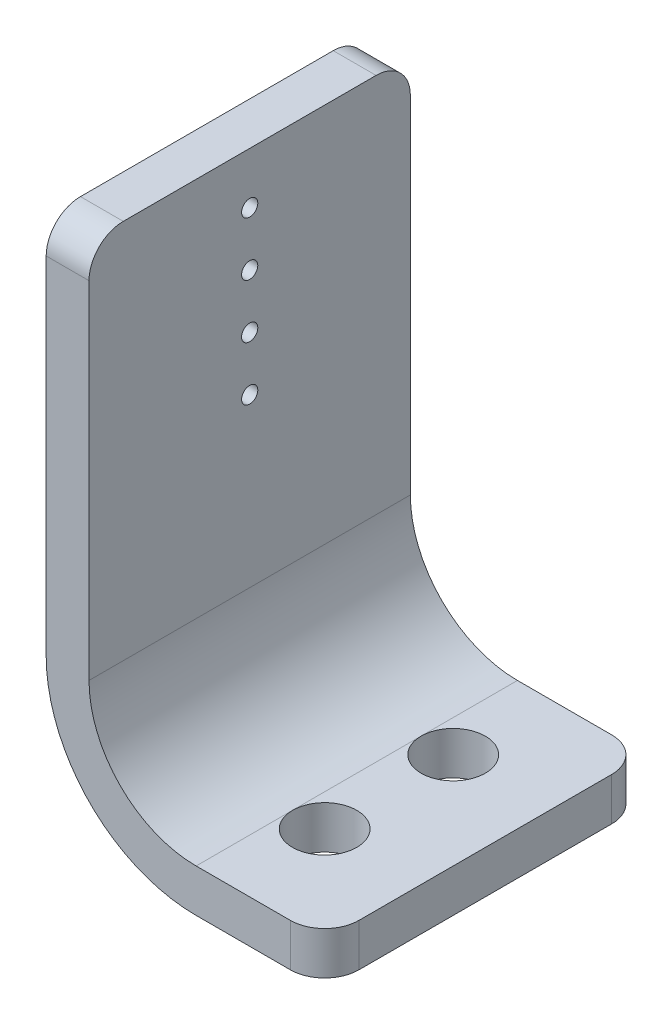
SolidWorks part; units mm, degrees
material "6061 Alloy"
ref_plane "Front Plane" through (0, 0, 0) normal (0, 0, 1) x (1, 0, 0)
ref_plane "Top Plane" through (0, 0, 0) normal (0, 1, 0) x (1, 0, 0)
ref_plane "Right Plane" through (0, 0, 0) normal (1, 0, 0) x (0, 0, -1)
sketch "Sketch1" plane through (0, 0, 0) normal (0, 0, 1) x (1, 0, 0)
  line L0 (0, 18.0956) -> (0, -10.0984)
  line L1 (7.9375, -18.0359) -> (17.4625, -18.0359)
  line L2 (-3.175, 18.0956) -> (-3.175, -10.0984)
  line L3 (7.9375, -21.2109) -> (17.4625, -21.2109)
  line L4 (0, 18.0956) -> (-3.175, 18.0956)
  line L5 (17.4625, -18.0359) -> (17.4625, -21.2109)
  arc A0 (7.9375, -18.0359) -> (0, -10.0984) centre (7.9375, -10.0984) cw
  arc A1 (7.9375, -21.2109) -> (-3.175, -10.0984) centre (7.9375, -10.0984) cw
  dimension "D1" = 7.9375
  dimension "D3" = 9.525
  dimension "D4" = 28.194
  dimension "D2" = 3.175
extrude "Boss-Extrude1" add sketch "Sketch1" along normal blind 23.8125
sketch "Sketch2" plane through (-3.175, 0, 0) normal (-1, 0, 0) x (0, 0, 1)
  line L0 (23.8125, 18.0956) -> (0, 18.0956) construction
  line L1 (23.8125, 18.0956) -> (0, 18.0956) construction
  line L2 (11.9063, 14.2856) -> (8.4563, 14.2856)
  line L6 (9.2563, 12.0766) -> (9.9092, 0.1265)
  line L7 (14.5563, 12.0766) -> (13.9033, 0.1265)
  arc A6 (14.5563, 12.0766) -> (9.2563, 12.0766) centre (11.9063, 14.2856) ccw
  arc A7 (9.9092, 0.1265) -> (13.9033, 0.1265) centre (11.9063, 0.2356) ccw
  circle A8 centre (11.9063, 2.2857) radius 0.6
  circle A11 centre (11.9063, 6.2857) radius 0.6
  circle A15 centre (11.9063, 10.2856) radius 0.6
  circle A17 centre (11.9063, 14.2856) radius 0.6
  point P2 (11.9063, 2.2857)
  point P9 (11.9063, 6.2857)
  point P10 (11.9063, 2.2857)
  point P13 (11.9063, 18.0956)
  point P14 (11.9063, 2.2857)
  dimension "D1" = 6.9
  dimension "D2" = 4
  dimension "D7" = 1.2
  dimension "D8" = 4
  dimension "D3" = 11.95
  dimension "D4" = 0.653
  dimension "D5" = 5.3
  dimension "D6" = 3.994
  dimension "D9" = 4
  dimension "D11" = 4
  dimension "D12" = 3.81
extrude "Cut-Extrude1" cut sketch "Sketch2" against normal up to next from surface contours A17 | A15 | A11 | A8 starting at face at (-3.175, 3.9986, 11.9062)
sketch "Sketch5" plane through (0, -18.0359, 0) normal (0, 1, 0) x (1, 0, 0)
  line L0 (17.4625, 0) -> (7.9375, 0) construction
  line L2 (7.9375, -23.8125) -> (7.9375, 0) construction
  line L3 (17.4625, -23.8125) -> (7.9375, -23.8125) construction
  circle A0 centre (10.3187, -7.1437) radius 2.3813
  circle A1 centre (10.3187, -16.6687) radius 2.3813
  point P0 (10.3187, -8.6939)
  point P12 (19.8437, -11.9062)
  dimension "D1" = 4.7625
  dimension "D2" = 4.7625
  dimension "D3" = 7.1437
  dimension "D4" = 7.1437
extrude "Cut-Extrude2" cut sketch "Sketch5" against normal up to next
fillet "Fillet1" radius 2.54 4 edges at (17.4625, -19.6234, 0) (17.4625, -19.6234, 23.8125) (-1.5875, 18.0956, 0) (-1.5875, 18.0956, 23.8125)
sketch "Sketch3" plane through (-3.175, 0, 0) normal (-1, 0, 0) x (0, 0, 1)
  line L0 (11.9062, 18.0956) -> (11.9062, -10.0984)
  line L1 (21.2725, 18.0956) -> (2.54, 18.0956) construction
  line L2 (23.8125, -10.0984) -> (0, -10.0984) construction
sketch "Sketch6" plane through (0, -21.2109, 0) normal (0, -1, 0) x (1, 0, 0)
  line L0 (7.9375, 11.9062) -> (17.4625, 11.9062) construction
  line L1 (7.9375, 16.6687) -> (7.9375, 7.1437) construction
  line L2 (17.4625, 21.2725) -> (17.4625, 2.54) construction
